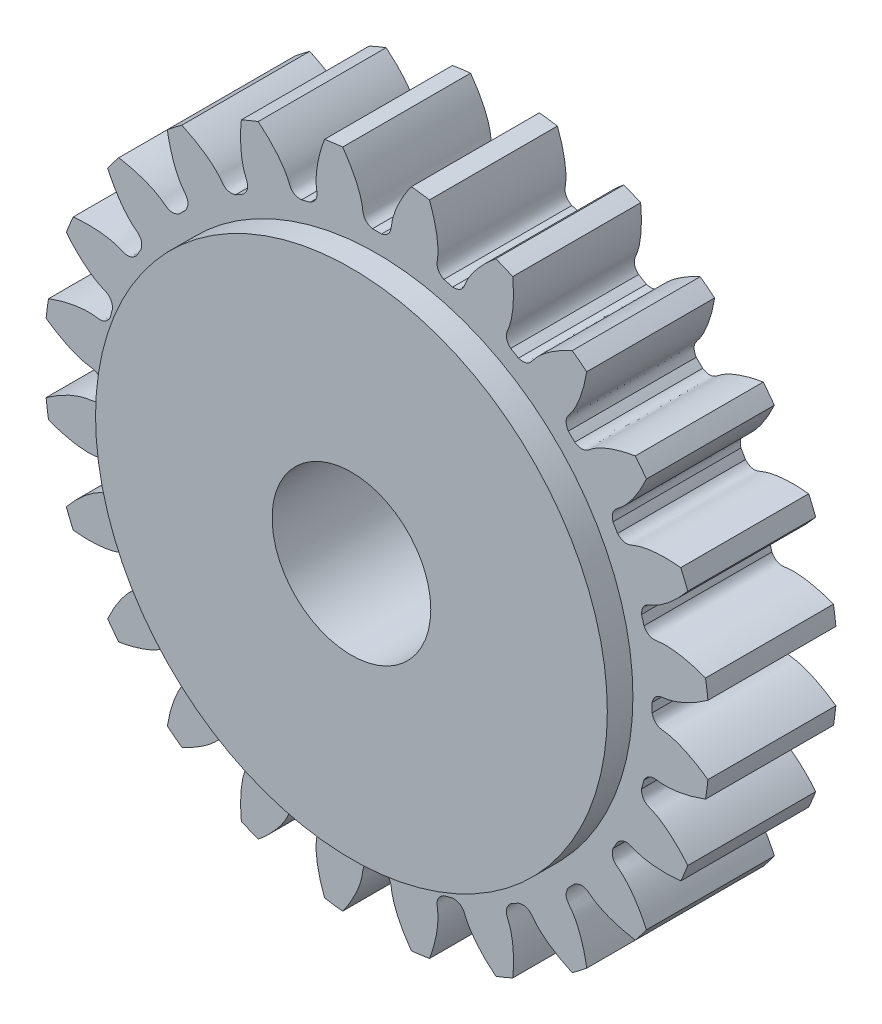
SolidWorks part; units mm, degrees
ref_plane "前视基准面" through (0, 0, 0) normal (0, 0, 1) x (1, 0, 0)
ref_plane "上视基准面" through (0, 0, 0) normal (0, 1, 0) x (1, 0, 0)
ref_plane "右视基准面" through (0, 0, 0) normal (1, 0, 0) x (0, 0, -1)
other "Configuration Table"
sketch "草图1" plane through (0, 0, 0) normal (0, 0, 1) x (1, 0, 0)
  circle A0 centre (0, 0) radius 6.5
extrude "凸台-拉伸1" add sketch "草图1" along normal blind 2.5
ref_axis "基准轴1" through (0, 0, 2.5) along (0, 0, -1)
sketch "草图2" plane through (0, 0, 0) normal (0, 0, 1) x (1, 0, 0)
  line L0 (0, 0) -> (0, 6.5) construction
  circle A0 centre (0, 0) radius 6.5 construction
  arc A1 (0.0884, 5.3743) -> (-0.0884, 5.3743) centre (0, 0) ccw
  arc A2 (1.5578, 7.3471) -> (-1.5578, 7.3471) centre (0, 0) ccw
  spline S0 degree 3 poles (0.0884, 5.3743) (0.284, 5.4284) (0.2695, 5.5579) (0.2931, 5.6863) (0.2965, 5.7029) (0.3007, 5.7216) (0.3058, 5.7424) (0.312, 5.7653) (0.3191, 5.7902) (0.3275, 5.8171) (0.3371, 5.846) (0.348, 5.8769) (0.3604, 5.9096) (0.3742, 5.9441) (0.3896, 5.9805) (0.4067, 6.0185) (0.4254, 6.0583) (0.446, 6.0997) (0.4684, 6.1427) (0.4928, 6.1872) (0.5192, 6.2332) (0.5476, 6.2806) (0.5782, 6.3293) (0.611, 6.3792) (0.6461, 6.4304) (0.6834, 6.4827) (0.7232, 6.536) (0.7654, 6.5903) (0.8101, 6.6456) (0.8574, 6.7016) (0.9073, 6.7583) (0.9598, 6.8158) (1.015, 6.8738) (1.0729, 6.9322) (1.1336, 6.9911) (1.1972, 7.0503) (1.2635, 7.1097) (1.3328, 7.1693) (1.4302, 7.2497) (1.506, 7.3084) (1.5578, 7.3471) knots 0 0 0 0 0.143961 0.149818 0.156577 0.164236 0.172796 0.182258 0.19262 0.203884 0.216049 0.229115 0.243082 0.25795 0.273719 0.290389 0.30796 0.326433 0.345806 0.366081 0.387257 0.409333 0.432311 0.45619 0.48097 0.506651 0.533234 0.560717 0.589101 0.618387 0.648574 0.679661 0.71165 0.74454 0.778331 0.813023 0.848616 0.885111 0.922506 1 1 1 1
  spline S1 degree 3 poles (-0.0884, 5.3743) (-0.284, 5.4284) (-0.2695, 5.5579) (-0.2931, 5.6863) (-0.2965, 5.7029) (-0.3007, 5.7216) (-0.3058, 5.7424) (-0.312, 5.7653) (-0.3191, 5.7902) (-0.3275, 5.8171) (-0.3371, 5.846) (-0.348, 5.8769) (-0.3604, 5.9096) (-0.3742, 5.9441) (-0.3896, 5.9805) (-0.4067, 6.0185) (-0.4254, 6.0583) (-0.446, 6.0997) (-0.4684, 6.1427) (-0.4928, 6.1872) (-0.5192, 6.2332) (-0.5476, 6.2806) (-0.5782, 6.3293) (-0.611, 6.3792) (-0.6461, 6.4304) (-0.6834, 6.4827) (-0.7232, 6.536) (-0.7654, 6.5903) (-0.8101, 6.6456) (-0.8574, 6.7016) (-0.9073, 6.7583) (-0.9598, 6.8158) (-1.015, 6.8738) (-1.0729, 6.9322) (-1.1336, 6.9911) (-1.1972, 7.0503) (-1.2635, 7.1097) (-1.3328, 7.1693) (-1.4302, 7.2497) (-1.506, 7.3084) (-1.5578, 7.3471) knots 0 0 0 0 0.143961 0.149818 0.156577 0.164236 0.172796 0.182258 0.19262 0.203884 0.216049 0.229115 0.243082 0.25795 0.273719 0.290389 0.30796 0.326433 0.345806 0.366081 0.387257 0.409333 0.432311 0.45619 0.48097 0.506651 0.533234 0.560717 0.589101 0.618387 0.648574 0.679661 0.71165 0.74454 0.778331 0.813023 0.848616 0.885111 0.922506 1 1 1 1
extrude "切除-拉伸1" cut sketch "草图2" along normal through all
pattern_circular "阵列(圆周)1" count 24 every 15 about axis through (0, 0, 2.5) along (0, 0, -1) of "切除-拉伸1"
sketch "草图3" plane through (0, 0, 0) normal (0, 0, 1) x (1, 0, 0)
  circle A0 centre (0, 0) radius 6 construction
  dimension "Dn" = 12
sketch "草图6" plane through (0, 0, 2.5) normal (0, 0, 1) x (1, 0, 0)
  circle A0 centre (0, 0) radius 5
  dimension "D1" = 10
extrude "凸台-拉伸2" add sketch "草图6" along normal blind 0.5
sketch "草图4" plane through (0, 0, 2.5) normal (0, 0, 1) x (1, 0, 0)
  circle A0 centre (0, 0) radius 1.55
  dimension "D1" = 3.1
extrude "切除-拉伸2" cut sketch "草图4" against normal mid plane 10
